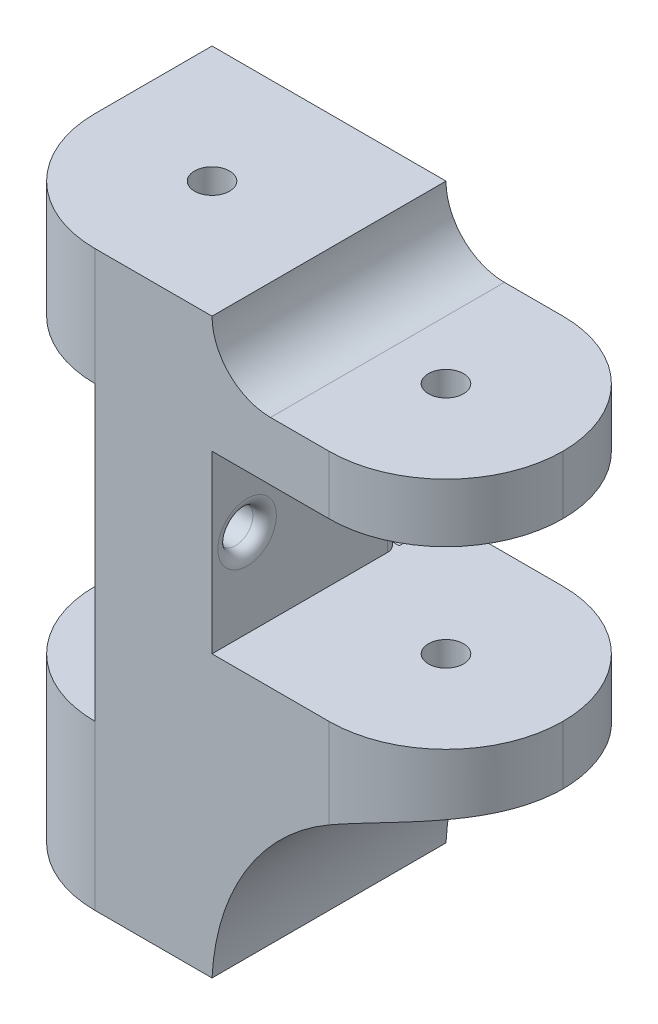
SolidWorks part; units mm, degrees
ref_plane "Alzado" through (0, 0, 0) normal (0, 0, 1) x (1, 0, 0)
ref_plane "Planta" through (0, 0, 0) normal (0, 1, 0) x (1, 0, 0)
ref_plane "Vista lateral" through (0, 0, 0) normal (1, 0, 0) x (0, 0, -1)
sketch "Croquis1" plane through (0, 0, 0) normal (0, 0, 1) x (1, 0, 0)
  line L0 (0, 0) -> (0, 49)
  line L1 (0, 49) -> (20, 49)
  line L2 (0, 0) -> (20, 0)
  line L4 (25, 44) -> (40, 44)
  line L5 (0, 45) -> (0, 20)
  line L6 (39.975, 19) -> (40, 19)
  line L7 (40, 44) -> (40, 19)
  arc A0 (39.975, 19) -> (20, 0) centre (39.975, -1) ccw
  arc A1 (20, 49) -> (25, 44) centre (25, 49) ccw
  dimension "D7" = 40
  dimension "D8" = 10
  dimension "D1" = 49
  dimension "D2" = 20
  dimension "D3" = 20
  dimension "D4" = 25
  dimension "D5" = 40
  dimension "D6" = 5
extrude "Saliente-Extruir1" add sketch "Croquis1" along normal blind 20 contours A1 L1 L0 L2 A0 L6 L7 L4
sketch "Croquis2" plane through (0, 0, 0) normal (0, -1, 0) x (1, 0, 0)
  line L0 (0, 0) -> (20, 0) construction
  line L1 (0, 20) -> (0, 0) construction
  circle A0 centre (10, 10) radius 1.5
  dimension "D1" = 3
  dimension "D2" = 10
  dimension "D3" = 10
extrude "Cortar-Extruir1" cut sketch "Croquis2" against normal blind 50
sketch "Croquis5" plane through (40, 0, 0) normal (1, 0, 0) x (0, 0, -1)
  line L0 (-20, 44) -> (-20, 19) construction
  line L1 (-20, 39) -> (0, 39)
  line L2 (-20, 39) -> (-20, 24)
  line L3 (-20, 24) -> (0, 24)
  line L4 (0, 39) -> (0, 24)
  line L5 (0, 44) -> (0, 19) construction
  line L6 (-20, 19) -> (0, 19) construction
  dimension "D1" = 15
  dimension "D2" = 5
extrude "Cortar-Extruir3" cut sketch "Croquis5" against normal blind 20
sketch "Croquis7" plane through (20, 0, 0) normal (1, 0, 0) x (0, 0, -1)
  line L0 (-20, 39) -> (-20, 24) construction
  line L1 (0, 39) -> (-20, 39) construction
  circle A0 centre (-17, 31.5) radius 1.5
  dimension "D2" = 3
  dimension "D1" = 3
  dimension "D3" = 7.5
extrude "Cortar-Extruir5" cut sketch "Croquis7" against normal blind 30
fillet "Redondeo2" radius 10 1 edges at (0, 24.5, 20)
sketch "Croquis6" plane through (0, 44, 0) normal (0, 1, 0) x (1, 0, 0)
  line L0 (40, -20) -> (40, 0) construction
  line L1 (25, -20) -> (40, -20) construction
  circle A0 centre (30, -10) radius 1.5
  dimension "D1" = 3
  dimension "D2" = 10
  dimension "D3" = 10
extrude "Cortar-Extruir4" cut sketch "Croquis6" against normal blind 30
sketch "Croquis8" plane through (0, 0, 0) normal (-1, 0, 0) x (0, 0, 1)
  line L1 (13, 39) -> (20, 39)
  line L3 (13, 24) -> (20, 24)
  line L4 (20, 39) -> (20, 24)
  line L5 (20, 49) -> (20, 0) construction
  line L6 (20, 49) -> (10, 49) construction
  line L8 (13, 24) -> (13, 39)
  dimension "D1" = 15
  dimension "D2" = 10
  dimension "D3" = 7
fillet "Redondeo3" radius 10 4 edges at (40, 21.5, 0) (40, 41.5, 0) (40, 21.5, 20) (40, 41.5, 20)
extrude "Cortar-Extruir6" cut sketch "Croquis8" against normal blind 10
sketch "Sketch1" plane through (0, 0, 0) normal (0, 0, -1) x (-1, 0, 0)
  line L0 (0, 0) -> (0, 49) construction
  line L1 (0, 24) -> (-3, 24)
  line L2 (0, 24) -> (0, 39)
  line L3 (0, 39) -> (-3, 39)
  line L4 (-3, 24) -> (-3, 39)
  line L5 (-20, 39) -> (-30, 39) construction
  dimension "D1" = 15
  dimension "D2" = 3
  dimension "D3" = 0
extrude "Cut-Extrude1" cut sketch "Sketch1" against normal blind 20
fillet "Fillet1" radius 5 1 edges at (3, 31.5, 13)
sketch "Sketch2" plane through (0, 0, 0) normal (0, 0, -1) x (-1, 0, 0)
  line L4 (-20, 24) -> (-20, 39) construction
  line L5 (-20, 34.5) -> (-14, 34.5)
  line L6 (-20, 34.5) -> (-20, 22.5)
  line L7 (-20, 22.5) -> (-14, 22.5)
  line L10 (-3, 24) -> (0, 24) construction
  line L12 (0, 0) -> (-20, 0) construction
  line L13 (0, 0) -> (0, 24) construction
  line L15 (-6, 16) -> (0, 16)
  line L17 (-6, 4) -> (0, 4)
  line L18 (0, 16) -> (0, 4)
  arc A1 (-14, 22.5) -> (-14, 34.5) centre (-14, 28.5) ccw
  arc A2 (-6, 16) -> (-6, 4) centre (-6, 10) ccw
  dimension "D2" = 1.5
  dimension "D4" = 12
  dimension "D1" = 12
  dimension "D3" = 10
  dimension "D5" = 6
  dimension "D6" = 6
  dimension "D7" = 6
extrude "Cut-Extrude2" cut sketch "Sketch2" against normal blind 4
sketch "Sketch3" plane through (0, 0, 4) normal (0, 0, -1) x (-1, 0, 0)
  line L1 (-20, 22.5) -> (-14, 22.5) construction
  line L4 (-20, 34.5) -> (-20, 24) construction
  circle A0 centre (-14, 28.5) radius 3
  circle A1 centre (-6, 10) radius 3
  dimension "D3" = 6
  dimension "D4" = 6
  dimension "D1" = 6
  dimension "D2" = 6
sketch "Sketch5" plane through (0, 0, 0) normal (-1, 0, 0) x (0, 0, 1)
  line L1 (6, 24) -> (20, 24)
  line L2 (6, 24) -> (6, 14)
  line L3 (6, 14) -> (20, 14)
  line L4 (20, 24) -> (20, 14)
  line L5 (13, 24) -> (20, 24) construction
  dimension "D1" = 14
  dimension "D2" = 10
  dimension "D3" = 0
  dimension "D4" = 0
extrude "Cut-Extrude3" cut sketch "Sketch5" against normal blind 10
sketch "Sketch6" plane through (10, 0, 0) normal (-1, 0, 0) x (0, 0, 1)
  line L0 (12, 16) -> (12, 22)
  line L1 (14, 22) -> (14, 16)
  line L2 (20, 39) -> (20, 14) construction
  line L3 (11.5, 14) -> (20, 14) construction
  arc A0 (14, 22) -> (12, 22) centre (13, 22) ccw
  arc A1 (12, 16) -> (14, 16) centre (13, 16) ccw
  dimension "D2" = 2
  dimension "D3" = 2
  dimension "D1" = 6
  dimension "D4" = 8
  dimension "D5" = 2
fillet "Fillet6" radius 5 1 edges at (0, 19, 6)
extrude "Cut-Extrude4" cut sketch "Sketch6" against normal blind 16
extrude "Boss-Extrude1" add sketch "Sketch3" along normal blind 2
sketch "Sketch4" plane through (0, 0, 2) normal (0, 0, -1) x (-1, 0, 0)
  circle A0 centre (-14, 28.5) radius 4
  circle A1 centre (-6, 10) radius 4
  dimension "D1" = 8
  dimension "D2" = 8
extrude "Boss-Extrude2" add sketch "Sketch4" along normal blind 2
fillet "Fillet2" radius 1 4 edges at (11, 28.5, 2) (11, 28.5, 4) (3, 10, 2) (3, 10, 4)
fillet "Fillet3" radius 1 3 edges at (20, 29.25, 4) (0, 9, 4) (0.5, 14, 4)
fillet "Fillet4" radius 1 2 edges at (20, 31.5, 15.5) (10, 31.5, 18.5)
fillet "Fillet9" radius 0.5 4 edges at (10, 15, 13) (10, 23, 13) (10, 19, 14) (10, 19, 12)
